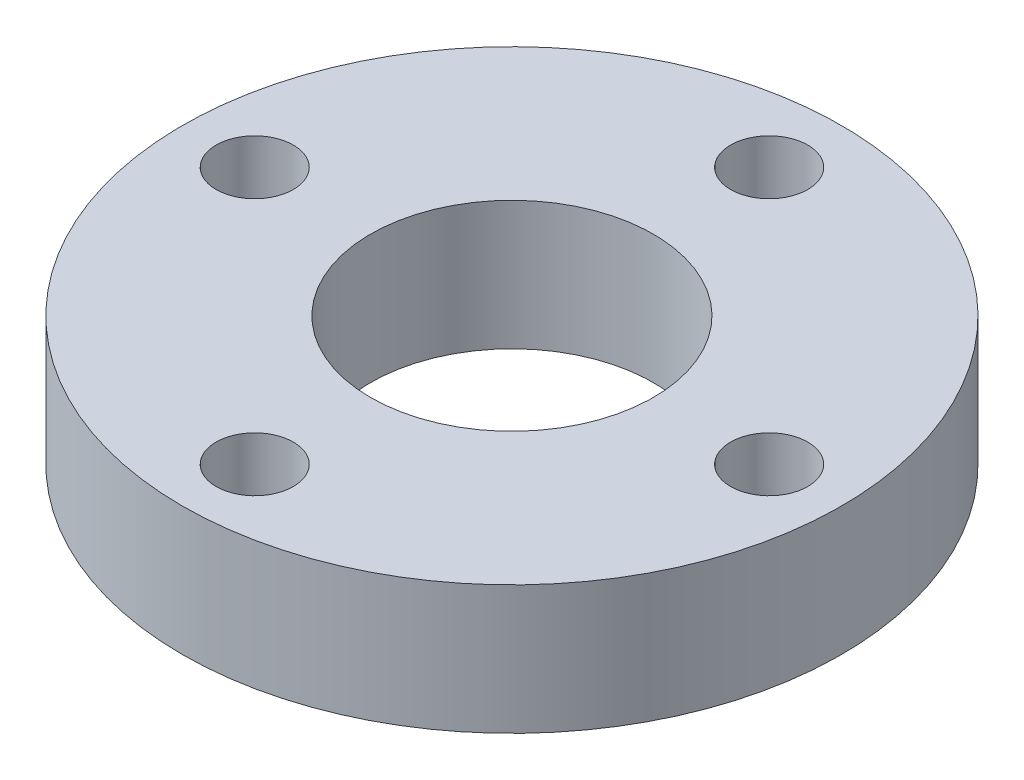
SolidWorks part; units mm, degrees
ref_plane "Front Plane" through (0, 0, 0) normal (0, 0, 1) x (1, 0, 0)
ref_plane "Top Plane" through (0, 0, 0) normal (0, 1, 0) x (1, 0, 0)
ref_plane "Right Plane" through (0, 0, 0) normal (1, 0, 0) x (0, 0, -1)
sketch "Sketch1" plane through (0, 0, 0) normal (0, 1, 0) x (1, 0, 0)
  circle A0 centre (0, 0) radius 10.25
  circle A1 centre (0, 0) radius 4.4
  circle A2 centre (0, 0) radius 8
  circle A3 centre (0, 8) radius 1.2
  circle A4 centre (8, 0) radius 1.2
  circle A5 centre (0, -8) radius 1.2
  circle A6 centre (-8, 0) radius 1.2
  point P16 (0, 0)
  dimension "D1" = 20.5
  dimension "D2" = 8.8
  dimension "D3" = 2.4
  dimension "D4" = 4
extrude "Boss-Extrude1" add sketch "Sketch1" along normal blind 4 contours A0 A6 A2 A3 A4 A5 | A6 A2 A5 A4 A3 A1 region at (-9.9601, 0, 0) region at (6.5763, 0, 0)
